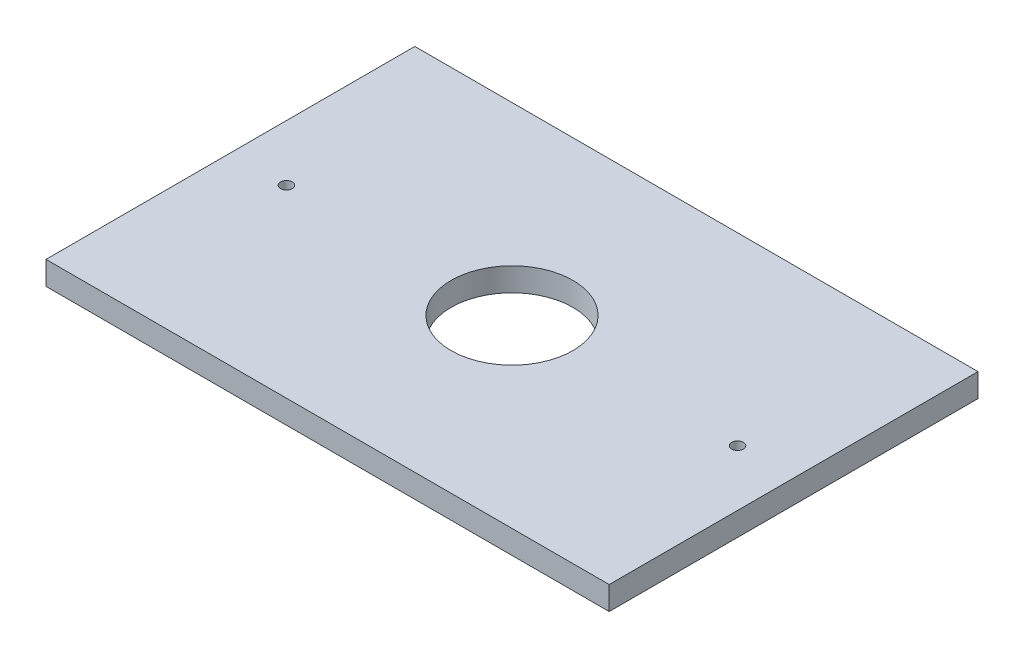
SolidWorks part; units mm, degrees
material "Oak"
ref_plane "Front Plane" through (0, 0, 0) normal (0, 0, 1) x (1, 0, 0)
ref_plane "Top Plane" through (0, 0, 0) normal (0, 1, 0) x (1, 0, 0)
ref_plane "Right Plane" through (0, 0, 0) normal (1, 0, 0) x (0, 0, -1)
sketch "Sketch1" plane through (0, 0, 0) normal (0, 1, 0) x (1, 0, 0)
  line L1 (0, 0) -> (152.7, 0)
  line L2 (0, 0) -> (0, 100)
  line L3 (0, 100) -> (152.7, 100)
  line L4 (152.7, 0) -> (152.7, 100)
  dimension "D1" = 152.7
  dimension "D2" = 100
extrude "Boss-Extrude1" add sketch "Sketch1" along normal blind 6.35
sketch "Sketch2" plane through (0, 6.35, 0) normal (0, 1, 0) x (1, 0, 0)
  line L0 (76.35, 100) -> (76.35, 0) construction
  line L1 (152.7, 100) -> (0, 100) construction
  line L2 (0, 0) -> (152.7, 0) construction
  line L3 (0, 50) -> (152.7, 50) construction
  line L4 (0, 100) -> (0, 0) construction
  line L5 (152.7, 0) -> (152.7, 100) construction
  circle A0 centre (76.35, 50) radius 16.51
  dimension "D1" = 33.02
extrude "Cut-Extrude1" cut sketch "Sketch2" against normal blind 10
sketch "Sketch3" plane through (0, 6.35, 0) normal (0, 1, 0) x (1, 0, 0)
  line L0 (0, 100) -> (0, 0) construction
  line L1 (152.7, 100) -> (0, 100) construction
  line L3 (152.7, 0) -> (152.7, 100) construction
  circle A0 centre (15.2, 50) radius 1.5875
  circle A1 centre (137.5, 50) radius 1.5875
  point P0 (0, 50)
  point P1 (76.35, 100)
  point P4 (15.2, 50)
  point P7 (137.5, 50)
  point P14 (0, 0)
  point P15 (0, 0)
  dimension "D1" = 3.175
  dimension "D2" = 3.175
  dimension "D3" = 15.2
  dimension "D4" = 15.2
  dimension "D5" = 50
  dimension "D6" = 50
extrude "Cut-Extrude2" cut sketch "Sketch3" against normal blind 10
